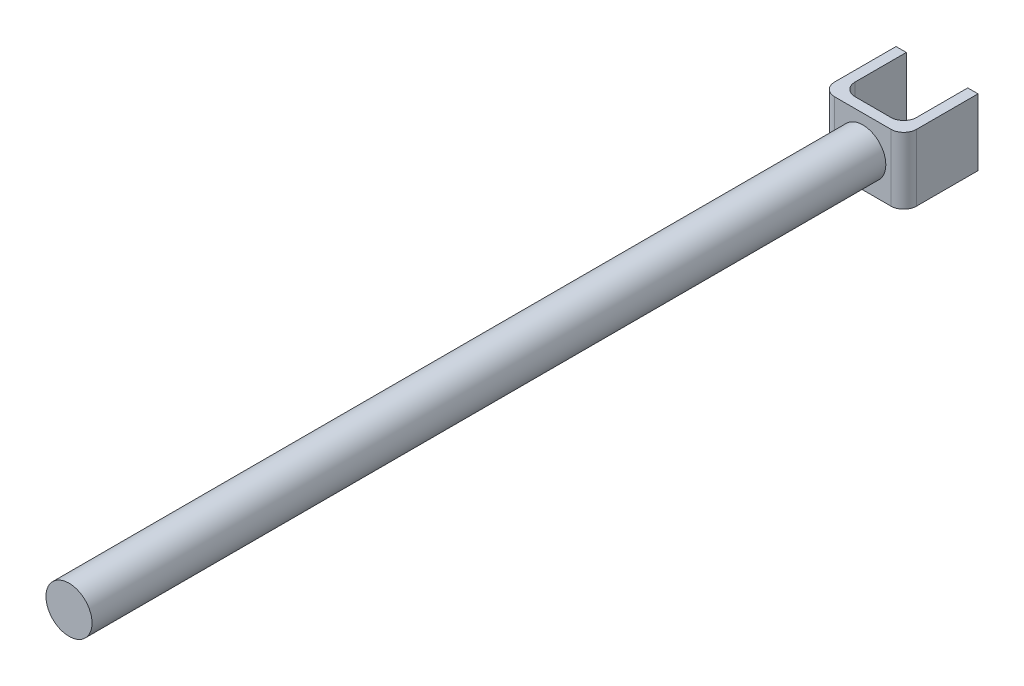
SolidWorks part; units mm, degrees
ref_plane "Front Plane" through (0, 0, 0) normal (0, 0, 1) x (1, 0, 0)
ref_plane "Top Plane" through (0, 0, 0) normal (0, 1, 0) x (1, 0, 0)
ref_plane "Right Plane" through (0, 0, 0) normal (1, 0, 0) x (0, 0, -1)
sketch "Sketch1" plane through (0, 0, 0) normal (0, 1, 0) x (1, 0, 0)
  line L0 (0, 0) -> (0, -20.7763) construction
  line L1 (7, -20.7763) -> (-7, -20.7763)
  line L2 (12, -15.7763) -> (12, 4.2237)
  line L3 (12, 4.2237) -> (16, 4.2237)
  line L4 (16, 4.2237) -> (16, -19.7763)
  line L5 (11, -24.7763) -> (-11, -24.7763)
  line L6 (-16, 4.2237) -> (-16, -19.7763)
  line L7 (-12, 4.2237) -> (-16, 4.2237)
  line L8 (-12, -15.7763) -> (-12, 4.2237)
  arc A0 (16, -19.7763) -> (11, -24.7763) centre (11, -19.7763) cw
  arc A1 (7, -20.7763) -> (12, -15.7763) centre (7, -15.7763) ccw
  arc A2 (-7, -20.7763) -> (-12, -15.7763) centre (-7, -15.7763) cw
  arc A3 (-16, -19.7763) -> (-11, -24.7763) centre (-11, -19.7763) ccw
  point P6 (0, -20.7763)
  point P13 (12, -20.7763)
  point P20 (0, -24.7763)
  point P22 (-12, -20.7763)
  dimension "D5" = 5
  dimension "D1" = 4
  dimension "D2" = 4
  dimension "D3" = 25
  dimension "D4" = 12
extrude "Boss-Extrude1" add sketch "Sketch1" along normal blind 13 and the other way blind 13
sketch "Sketch2" plane through (0, 0, 24.7763) normal (0, 0, 1) x (1, 0, 0)
  circle A0 centre (0, 0) radius 9
  dimension "D1" = 18
extrude "Boss-Extrude2" add sketch "Sketch2" along normal blind 310
sketch "Sketch3" plane through (0, 0, 0) normal (0, 1, 0) x (1, 0, 0)
  line L0 (0, 0) -> (0, -400) construction
  point P4 (0, -400)
  point P5 (0, 0)
  dimension "D1" = 400
